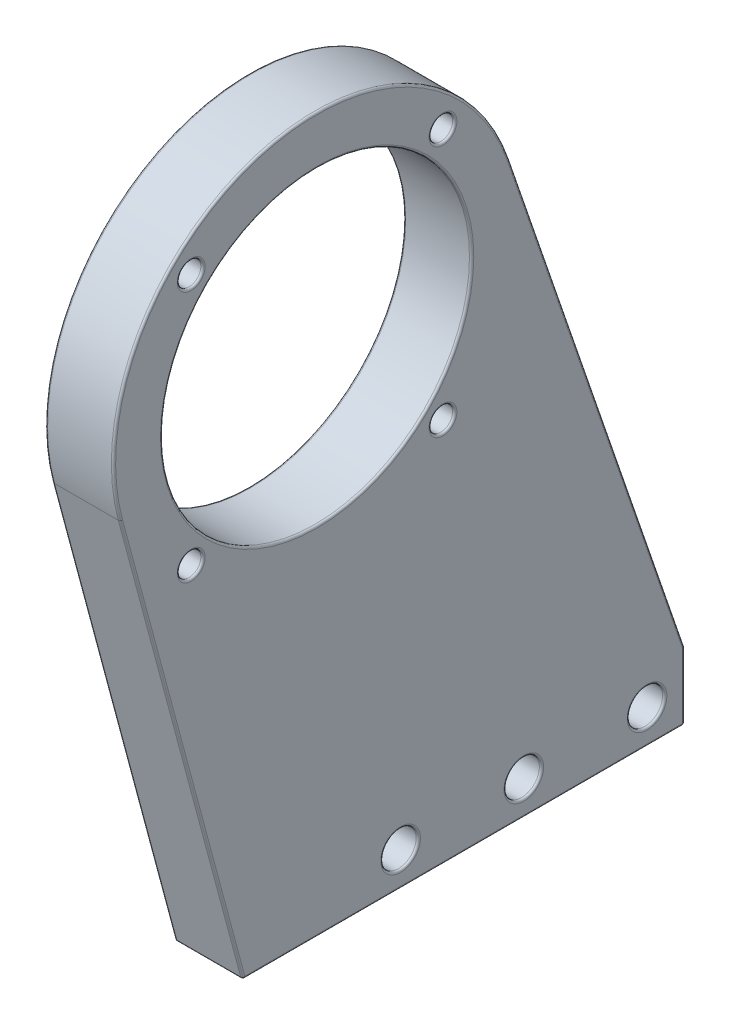
SolidWorks part; units mm, degrees
ref_plane "Front Plane" through (0, 0, 0) normal (0, 0, 1) x (1, 0, 0)
ref_plane "Top Plane" through (0, 0, 0) normal (0, 1, 0) x (1, 0, 0)
ref_plane "Right Plane" through (0, 0, 0) normal (1, 0, 0) x (0, 0, -1)
sketch "Sketch1" plane through (0, 0, 0) normal (1, 0, 0) x (0, 0, -1)
  line L0 (-36.7052, -9.8351) -> (-13.7915, -95.35)
  line L1 (-13.7915, -95.35) -> (68.5885, -95.35)
  line L2 (35.9367, 12.3514) -> (68.5885, -82.65)
  line L3 (68.5885, -82.65) -> (68.5885, -95.35)
  line L4 (68.5885, -89) -> (61.59, -89) construction
  line L5 (61.59, -89) -> (38.59, -89) construction
  line L6 (38.59, -89) -> (15.59, -89) construction
  line L7 (0, 0) -> (0, 38) construction
  line L8 (-23.5, 23.5) -> (23.5, 23.5) construction
  line L9 (-23.5, 23.5) -> (-23.5, -23.5) construction
  line L10 (-23.5, -23.5) -> (23.5, -23.5) construction
  line L11 (23.5, 23.5) -> (23.5, -23.5) construction
  line L12 (-23.5, 23.5) -> (23.5, -23.5) construction
  line L13 (-23.5, -23.5) -> (23.5, 23.5) construction
  circle A0 centre (0, 0) radius 28.85
  circle A1 centre (0, 0) radius 38
  circle A2 centre (61.59, -89) radius 3.3
  circle A3 centre (38.59, -89) radius 3.3
  circle A4 centre (15.59, -89) radius 3.3
  circle A5 centre (-23.5, 23.5) radius 2.2
  circle A6 centre (23.5, 23.5) radius 2.2
  circle A7 centre (-23.5, -23.5) radius 2.2
  circle A8 centre (23.5, -23.5) radius 2.2
  dimension "D1" = 57.7
  dimension "D2" = 76
  dimension "D7" = 23
  dimension "D8" = 6.6
  dimension "D12" = 4.4
  dimension "D3" = 82.38
  dimension "D4" = 12.7
  dimension "D5" = 120.65
  dimension "D6" = 105
  dimension "D9" = 6.35
  dimension "D10" = 15.59
  dimension "D11" = 47
extrude "Boss-Extrude1" add sketch "Sketch1" along normal blind 12.7 contours A1 A8 A7 A6 A5 A0 | A1 L0 L1 L3 L2 A4 A3 A2 region at (0, -60.5652, -20.821) region at (0, 35.3148, 10.7859)
chamfer "Chamfer1" distance 3 angle 45 3 edges at (0, -89, -18.89) (0, -89, -41.89) (0, -89, -64.89)
fillet "Fillet1" radius 0.4 32 edges at (12.7, -52.5926, 25.2484) (12.7, 36.3427, 11.0999) (0, -52.5926, 25.2484) (0, 36.3427, 11.0999) (0, 23.5, 21.3) (12.7, 23.5, 21.3) (0, 23.5, -25.7) (12.7, 23.5, -25.7) (0, 0, -28.85) (12.7, 0, -28.85) (0, -23.5, 21.3) (12.7, -23.5, 21.3) (0, -23.5, -25.7) (12.7, -23.5, -25.7) (12.7, -89, -68.5885) (0, -89, -68.5885) (6.35, -95.35, 13.7915) (12.7, -95.35, -27.3985) (6.35, -95.35, -68.5885) (0, -95.35, -27.3985) (6.35, -82.65, -68.5885) (12.7, -35.1493, -52.2626) (0, -35.1493, -52.2626) (0, -89, -21.89) (12.7, -89, -18.89) (3, -89, -18.89) (12.7, -89, -41.89) (0, -89, -44.89) (3, -89, -41.89) (0, -89, -67.89) (12.7, -89, -64.89) (3, -89, -64.89)
